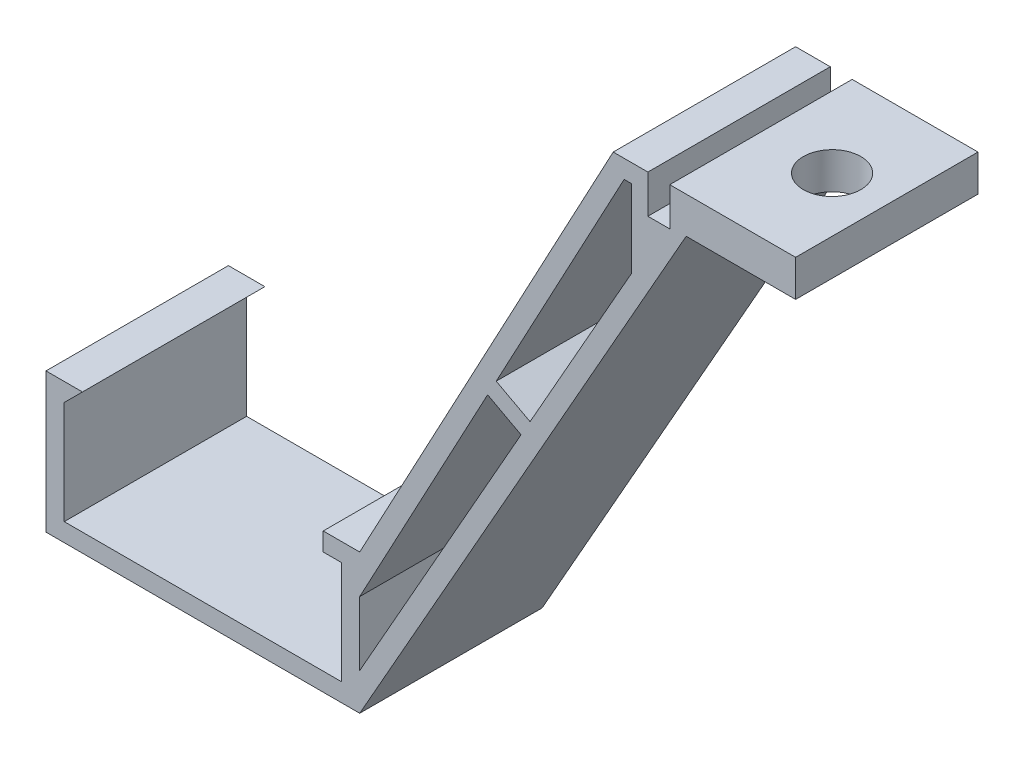
SolidWorks part; units mm, degrees
ref_plane "Front Plane" through (0, 0, 0) normal (0, 0, 1) x (1, 0, 0)
ref_plane "Top Plane" through (0, 0, 0) normal (0, 1, 0) x (1, 0, 0)
ref_plane "Right Plane" through (0, 0, 0) normal (1, 0, 0) x (0, 0, -1)
sketch "Sketch1" plane through (0, 0, 0) normal (0, 0, 1) x (1, 0, 0)
  line L0 (-15, 4.085) -> (-15, 15) construction
  line L1 (15, -15) -> (-15, -15) construction
  line L2 (15, -15) -> (15, -4.085) construction
  line L3 (15, 15) -> (-15, 15) construction
  line L4 (-15, -15) -> (-15, -4.085) construction
  line L5 (15, -15) -> (-15, 15) construction
  line L6 (15, 15) -> (-15, -15) construction
  line L7 (-15, 4.085) -> (-10, 4.085) construction
  line L9 (-15, -4.085) -> (-10, -4.085) construction
  line L10 (-10, 4.085) -> (-10, -4.085) construction
  line L11 (15, -4.085) -> (10, -4.085) construction
  line L13 (15, 4.085) -> (10, 4.085) construction
  line L14 (10, -4.085) -> (10, 4.085) construction
  line L15 (15, 4.085) -> (15, 15) construction
  line L16 (-15.2, -15.2) -> (-15.2, -3.885)
  line L25 (15.2, -3.885) -> (13.2, -3.885)
  line L26 (15.2, -15.2) -> (15.2, -3.885)
  line L27 (15.2, -15.2) -> (-15.2, -15.2)
  line L28 (-10.2, 3.885) -> (-10.2, -3.885) construction
  line L29 (-15.2, 3.885) -> (-10.2, 3.885) construction
  line L30 (-15.2, 3.885) -> (-15.2, 15.2) construction
  line L31 (15.2, 15.2) -> (-15.2, 15.2) construction
  line L32 (15.2, 3.885) -> (15.2, 15.2) construction
  line L33 (15.2, 3.885) -> (10.2, 3.885) construction
  line L34 (10.2, -3.885) -> (10.2, 3.885) construction
  line L35 (17.2, -1.885) -> (13.2, -1.885)
  line L36 (17.2, -17.2) -> (17.2, -1.885)
  line L37 (17.2, -17.2) -> (-17.2, -17.2)
  line L38 (-17.2, -17.2) -> (-17.2, -1.885)
  line L39 (-17.2, -1.885) -> (-13.2, -1.885)
  line L40 (13.2, -1.885) -> (13.2, -3.885)
  line L41 (-15.2, -3.885) -> (-13.2, -1.885)
  line L42 (-17.2, -1.885) -> (-10.2, -1.885) construction
  line L43 (-15.2, -3.885) -> (-10.2, -3.885) construction
  line L44 (17.2, -1.885) -> (10.2, -1.885) construction
  line L45 (15.2, -3.885) -> (10.2, -3.885) construction
  point P0 (0, 0)
  point P14 (-10, 0)
  point P15 (10, 0)
  dimension "D1" = 30
  dimension "D2" = 30
  dimension "D3" = 8.17
  dimension "D4" = 5
  dimension "D7" = 2
  dimension "D8" = 225
  dimension "D5" = 0.2
  dimension "D6" = 2
extrude "Boss-Extrude1" add sketch "Sketch1" along normal blind 20
sketch "Sketch2" plane through (0, 0, 0) normal (0, 0, -1) x (-1, 0, 0)
  line L0 (-15, -4.085) -> (-45, 50) construction
  line L1 (-45, 50) -> (-48.8, 50) construction
  line L2 (-51, 50) -> (-51, 86) construction
  line L3 (-51, 86) -> (-45, 86) construction
  line L4 (-45, 86) -> (-45, 84) construction
  line L5 (-45, 84) -> (-49, 84) construction
  line L6 (-49, 84) -> (-49, 52) construction
  line L7 (-49, 52) -> (-45, 52) construction
  line L8 (-45, 52) -> (-45, 50) construction
  line L9 (-51, 50) -> (-51, 46) construction
  line L10 (-51, 46) -> (-49, 46) construction
  line L11 (-49, 46) -> (-49, 50) construction
  line L12 (-45, 50) -> (-17.2, -1.885)
  line L13 (-45, 50) -> (-48.8, 50)
  line L14 (-53, 50) -> (-53, 46)
  line L15 (-53, 46) -> (-17.2, -17.2)
  line L16 (-17.2, -1.885) -> (-17.2, -6.1198)
  line L17 (-46.1974, 48) -> (-32.171, 21.8216)
  line L19 (-47, 39.4657) -> (-35.8798, 19.8344)
  line L22 (-46.1974, 48) -> (-51, 48) construction
  line L23 (-51, 46.5271) -> (-19.2, -9.6114) construction
  line L24 (-51, 48) -> (-51, 46.5271) construction
  line L25 (-46.1974, 48) -> (-47, 48)
  line L26 (-47, 48) -> (-47, 39.4657)
  line L27 (-46.1974, 48) -> (-19.2, -2.387) construction
  line L28 (-19.2, -2.387) -> (-19.2, -9.6114) construction
  line L29 (-17.2, -13.1422) -> (-17.2, -17.2)
  line L30 (-17.2, -1.885) -> (-17.2, -17.2) construction
  line L31 (-51.2, 50) -> (-51.2, 45.8)
  line L32 (-51.2, 45.8) -> (-48.8, 45.8)
  line L33 (-48.8, 45.8) -> (-48.8, 50)
  line L34 (-51.2, 50) -> (-53, 50)
  line L35 (-45, 50) -> (-53, 50) construction
  line L36 (-31.6987, 20.9401) -> (-35.3867, 18.9641) construction
  line L37 (-32.171, 21.8216) -> (-35.8798, 19.8344)
  line L38 (-31.2264, 20.0587) -> (-34.8937, 18.0937)
  line L39 (-32.171, 21.8216) -> (-35.859, 19.8455) construction
  line L40 (-31.2264, 20.0587) -> (-34.9145, 18.0826) construction
  line L41 (-34.8937, 18.0937) -> (-17.2, -13.1422)
  line L42 (-31.2264, 20.0587) -> (-17.2, -6.1198)
  line L43 (-31.6987, 20.9401) -> (-35.3867, 18.9641) construction
  dimension "D1" = 30
  dimension "D2" = 35
  dimension "D3" = 32
  dimension "D4" = 2
  dimension "D5" = 2
  dimension "D6" = 2
  dimension "D7" = 4
  dimension "D8" = 4
  dimension "D9" = 2
  dimension "D11" = 2
  dimension "D10" = 2
  dimension "D12" = 0.2
  dimension "D13" = 1
  dimension "D14" = 1
extrude "Boss-Extrude2" add sketch "Sketch2" against normal up to surface (20 mm away) up to face at (1.2, -7.6359, 20)
sketch "Sketch3" plane through (0, 0, 0) normal (0, 0, -1) x (-1, 0, 0)
  line L0 (-53, 50) -> (-53, 46) construction
  line L1 (-53, 50) -> (-65, 50)
  line L2 (-53, 50) -> (-53, 46)
  line L3 (-53, 46) -> (-65, 46)
  line L4 (-65, 50) -> (-65, 46)
  line L5 (-53, 46) -> (-17.2, -17.2) construction
  point P5 (0, 0)
  point P6 (0, 0)
  point P7 (-53, 46)
  dimension "D1" = 12
extrude "Boss-Extrude3" add sketch "Sketch3" against normal up to surface (20 mm away) up to face at (25.13, 4.7226, 20)
sketch "Sketch4" plane through (0, 50, 0) normal (0, 1, 0) x (1, 0, 0)
  line L0 (59, -20) -> (59, 0) construction
  line L2 (51.2, 0) -> (65, 0) construction
  line L3 (65, -20) -> (65, 0) construction
  line L4 (65, -20) -> (51.2, -20) construction
  circle A0 centre (59, -10) radius 3.15
  point P8 (59, -7.5)
  point P9 (0, 0)
  point P10 (59, -20)
  dimension "D1" = 6.3
  dimension "D2" = 6
extrude "Cut-Extrude1" cut sketch "Sketch4" against normal up to next
